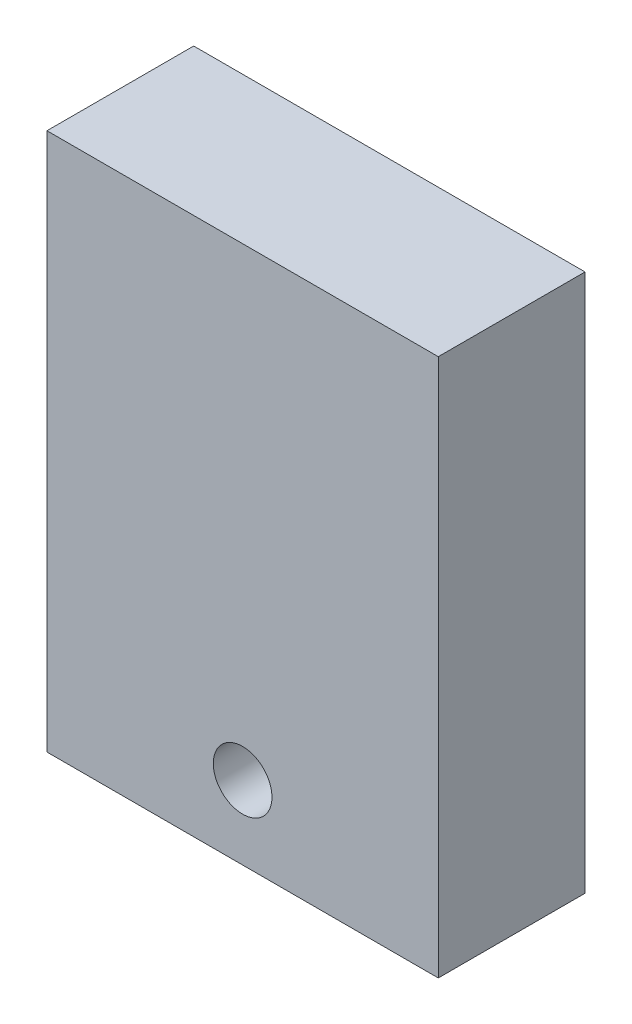
SolidWorks part; units mm, degrees
ref_plane "前视基准面" through (0, 0, 0) normal (0, 0, 1) x (1, 0, 0)
ref_plane "上视基准面" through (0, 0, 0) normal (0, 1, 0) x (1, 0, 0)
ref_plane "右视基准面" through (0, 0, 0) normal (1, 0, 0) x (0, 0, -1)
other "Configuration Table"
sketch "草图1" plane through (0, 0, 0) normal (0, 1, 0) x (1, 0, 0)
  line L1 (-4, -1.5) -> (4, -1.5)
  line L2 (-4, -1.5) -> (-4, 1.5)
  line L3 (-4, 1.5) -> (4, 1.5)
  line L4 (4, -1.5) -> (4, 1.5)
  line L5 (-4, -1.5) -> (4, 1.5) construction
  line L6 (-4, 1.5) -> (4, -1.5) construction
  point P0 (0, 0)
  dimension "D1" = 8
  dimension "D5" = 3
extrude "凸台-拉伸1" add sketch "草图1" along normal blind 3 contours L3 L4 L1 L2
sketch "草图2" plane through (0, 0, -1.5) normal (0, 0, -1) x (-1, 0, 0)
  line L0 (4, 3) -> (-4, 3) construction
  line L1 (-4, 3) -> (4, 3)
  line L2 (-4, 3) -> (-4, 11)
  line L3 (-4, 11) -> (4, 11)
  line L4 (4, 3) -> (4, 11)
  circle A0 centre (0, 7) radius 2.6
  point P6 (0, 0)
  point P8 (0, 6.8875)
  point P13 (-4, 7)
  dimension "D1" = 5.2
extrude "凸台-拉伸2" add sketch "草图2" against normal up to surface (3 mm away) contours L2 L3 L4 L1 up to face at (0, 1.5, 1.5)
extrude "切除-拉伸1" cut sketch "草图2<3>" against normal blind 0.8 contours A0
sketch "草图2<3>" plane through (0, 0, -1.5) normal (0, 0, -1) x (-1, 0, 0) same geometry as "草图2"
sketch "草图3" plane through (0, 0, -1.5) normal (0, 0, -1) x (-1, 0, 0)
  line L0 (0, 0) -> (0, 3) construction
  circle A0 centre (0, 1.5) radius 1
  circle A1 centre (0, 1.5) radius 0.6
  point P4 (0, 1.7092)
  dimension "D2" = 2
  dimension "D3" = 1.2
  dimension "D1" = 3
extrude "切除-拉伸2" cut sketch "草图3" against normal through all contours A1
extrude "切除-拉伸3" cut sketch "草图3<3>" against normal blind 1.5 contours A0
sketch "草图3<3>" plane through (0, 0, -1.5) normal (0, 0, -1) x (-1, 0, 0) same geometry as "草图3"
